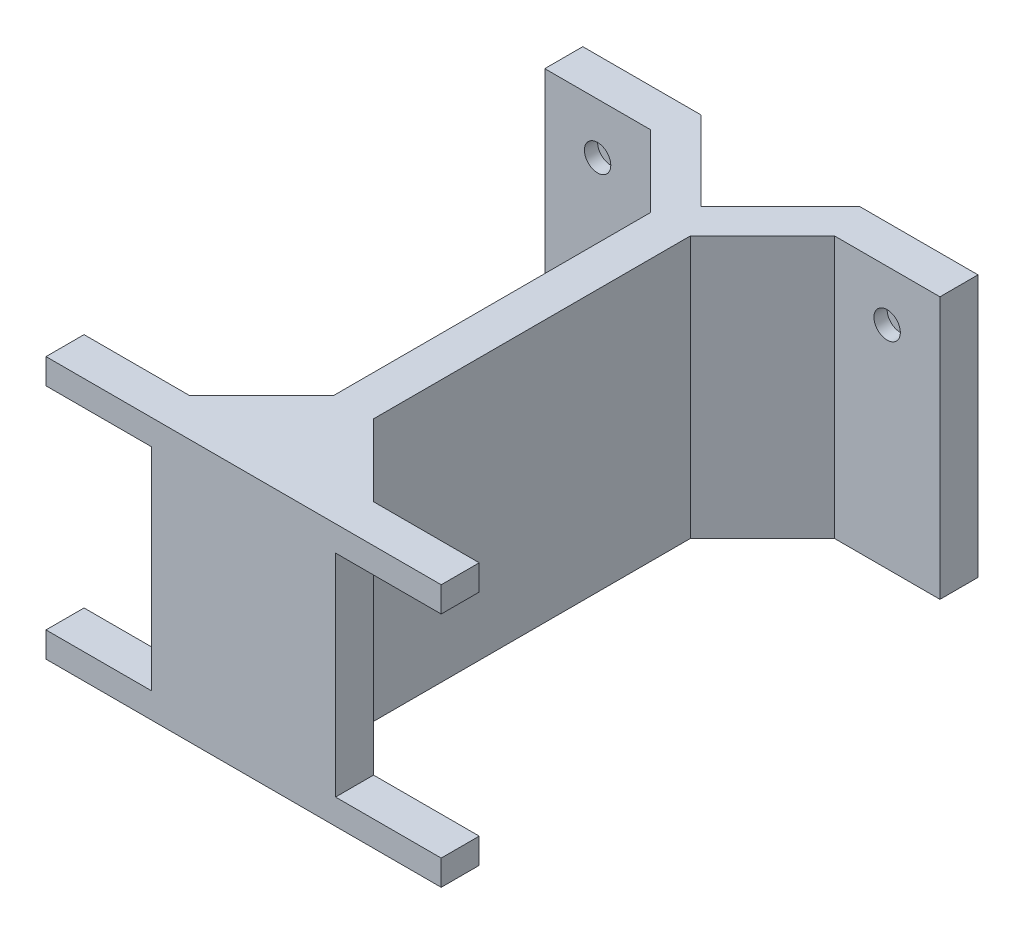
SolidWorks part; units mm, degrees
ref_plane "Front Plane" through (0, 0, 0) normal (0, 0, 1) x (1, 0, 0)
ref_plane "Top Plane" through (0, 0, 0) normal (0, 1, 0) x (1, 0, 0)
ref_plane "Right Plane" through (0, 0, 0) normal (1, 0, 0) x (0, 0, -1)
sketch "Sketch2" plane through (0, 0, 0) normal (0, 0, 1) x (1, 0, 0)
  line L1 (-40.6077, 18.1865) -> (34.1923, 18.1865)
  line L2 (-40.6077, 18.1865) -> (-40.6077, -31.4135)
  line L3 (-40.6077, -31.4135) -> (34.1923, -31.4135)
  line L4 (34.1923, 18.1865) -> (34.1923, -31.4135)
  dimension "D1" = 74.8
  dimension "D2" = 49.6
extrude "Boss-Extrude1" add sketch "Sketch2" along normal blind 101.6
sketch "Sketch3" plane through (0, 18.1865, 0) normal (0, 1, 0) x (1, 0, 0)
  line L0 (-40.6077, -7.2) -> (-20.6077, -7.2)
  line L1 (-40.6077, -101.6) -> (-40.6077, 0) construction
  line L2 (-20.6077, -7.2) -> (-7.0077, -20.8)
  line L3 (-7.0077, -20.8) -> (-7.0077, -80.8)
  line L4 (-7.0077, -80.8) -> (-20.6077, -94.4)
  line L5 (-20.6077, -94.4) -> (-40.6077, -94.4)
  line L6 (-40.6077, -94.4) -> (-40.6077, -7.2)
  line L7 (34.1923, -101.6) -> (-40.6077, -101.6) construction
  line L8 (34.1923, 0) -> (-40.6077, 0) construction
  dimension "D1" = 7.2
  dimension "D2" = 7.2
  dimension "D3" = 20
  dimension "D4" = 20
  dimension "D5" = 135
  dimension "D6" = 60
extrude "Cut-Extrude1" cut sketch "Sketch3" against normal blind 101.6
sketch "Sketch4" plane through (0, 18.1865, 0) normal (0, 1, 0) x (1, 0, 0)
  line L0 (34.1923, -94.4) -> (14.1923, -94.4)
  line L1 (34.1923, -101.6) -> (34.1923, 0) construction
  line L2 (14.1923, -94.4) -> (0.5923, -80.8)
  line L3 (0.5923, -80.8) -> (0.5923, -20.8)
  line L4 (0.5923, -20.8) -> (14.1923, -7.2)
  line L5 (14.1923, -7.2) -> (34.1923, -7.2)
  line L6 (34.1923, -7.2) -> (34.1923, -94.4)
  line L7 (34.1923, -101.6) -> (-40.6077, -101.6) construction
  line L8 (34.1923, 0) -> (-40.6077, 0) construction
  dimension "D1" = 7.2
  dimension "D2" = 7.2
  dimension "D3" = 20
  dimension "D4" = 20
  dimension "D5" = 135
  dimension "D6" = 135
  dimension "D7" = 60
extrude "Cut-Extrude2" cut sketch "Sketch4" against normal blind 101.6
sketch "Sketch5" plane through (0, 0, 101.6) normal (0, 0, 1) x (1, 0, 0)
  line L0 (34.1923, -31.4135) -> (34.1923, 18.1865) construction
  line L1 (34.1923, -26.6135) -> (14.1923, -26.6135)
  line L2 (34.1923, -26.6135) -> (34.1923, 13.3865)
  line L3 (34.1923, 13.3865) -> (14.1923, 13.3865)
  line L4 (14.1923, -26.6135) -> (14.1923, 13.3865)
  line L5 (-40.6077, -31.4135) -> (34.1923, -31.4135) construction
  line L6 (34.1923, 18.1865) -> (-40.6077, 18.1865) construction
  dimension "D1" = 4.8
  dimension "D2" = 40
  dimension "D3" = 20
extrude "Cut-Extrude3" cut sketch "Sketch5" against normal blind 10
sketch "Sketch6" plane through (0, 0, 101.6) normal (0, 0, 1) x (1, 0, 0)
  line L0 (-40.6077, 18.1865) -> (-40.6077, -31.4135) construction
  line L1 (-40.6077, 13.3865) -> (-20.6077, 13.3865)
  line L2 (-40.6077, 13.3865) -> (-40.6077, -26.6135)
  line L3 (-40.6077, -26.6135) -> (-20.6077, -26.6135)
  line L4 (-20.6077, 13.3865) -> (-20.6077, -26.6135)
  line L5 (34.1923, 18.1865) -> (-40.6077, 18.1865) construction
  dimension "D1" = 20
  dimension "D2" = 40
  dimension "D3" = 4.8
extrude "Cut-Extrude4" cut sketch "Sketch6" against normal blind 10
sketch "Sketch7" plane through (0, 0, 7.2) normal (0, 0, 1) x (1, 0, 0)
  line L0 (34.1923, 18.1865) -> (14.1923, 18.1865) construction
  line L1 (14.1923, -31.4135) -> (14.1923, 18.1865) construction
  circle A0 centre (24.1923, 8.5865) radius 2.5
  dimension "D1" = 9.6
  dimension "D2" = 10
extrude "Cut-Extrude5" cut sketch "Sketch7" against normal blind 2.5
sketch "Sketch8" plane through (0, 0, 7.2) normal (0, 0, 1) x (1, 0, 0)
  line L0 (-20.6077, 18.1865) -> (-40.6077, 18.1865) construction
  line L1 (-40.6077, -31.4135) -> (-40.6077, 18.1865) construction
  circle A0 centre (-30.6077, 8.5865) radius 2.5
  dimension "D1" = 9.6
  dimension "D2" = 10
extrude "Cut-Extrude6" cut sketch "Sketch8" against normal blind 2.5 contours A0
sketch "Sketch9" plane through (0, 18.1865, 0) normal (0, 1, 0) x (1, 0, 0)
  line L0 (-18.2482, 0) -> (-3.2077, -15.0405)
  line L1 (34.1923, 0) -> (-40.6077, 0) construction
  line L2 (-3.2077, -15.0405) -> (11.8328, 0)
  line L3 (11.8328, 0) -> (-18.2482, 0)
  line L4 (-7.0077, -20.8) -> (-20.6077, -7.2) construction
  line L5 (14.1923, -7.2) -> (0.5923, -20.8) construction
  line L6 (-40.6077, -7.2) -> (-40.6077, 0) construction
  point P13 (-40.8077, -1.9607)
  dimension "D1" = 37.4
extrude "Cut-Extrude7" cut sketch "Sketch9" against normal through all
